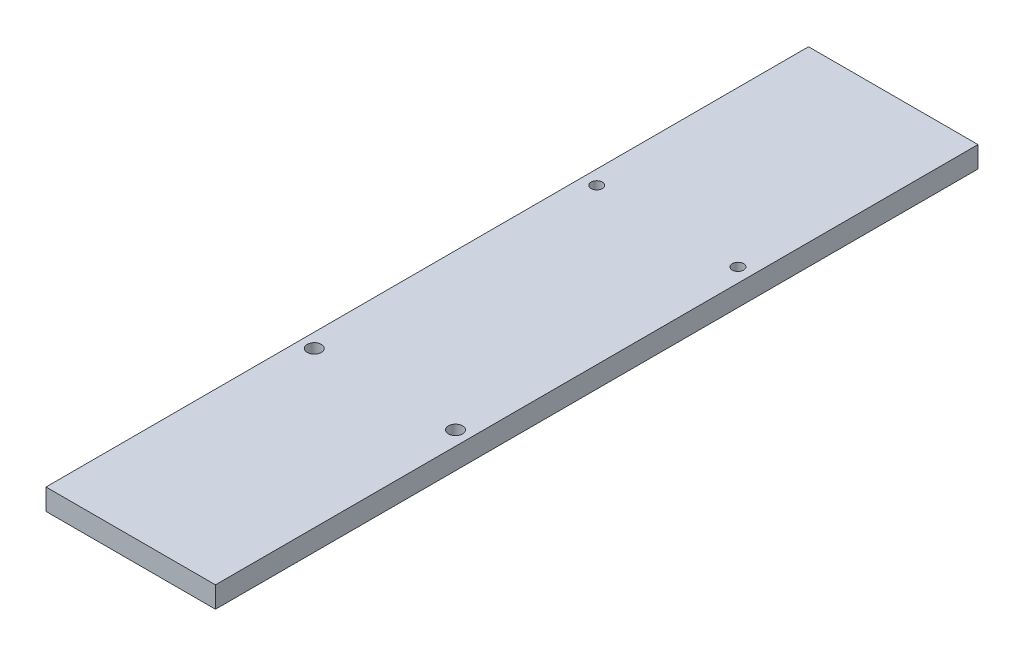
SolidWorks part; units mm, degrees
material "Cedar"
ref_plane "Front Plane" through (0, 0, 0) normal (0, 0, 1) x (1, 0, 0)
ref_plane "Top Plane" through (0, 0, 0) normal (0, 1, 0) x (1, 0, 0)
ref_plane "Right Plane" through (0, 0, 0) normal (1, 0, 0) x (0, 0, -1)
sketch "Sketch1" plane through (0, 0, 0) normal (0, 1, 0) x (1, 0, 0)
  line L1 (0, 0) -> (152.4, 0)
  line L2 (0, 0) -> (0, 685.8)
  line L3 (0, 685.8) -> (152.4, 685.8)
  line L4 (152.4, 0) -> (152.4, 685.8)
  dimension "D1" = 685.8
  dimension "D2" = 152.4
extrude "Boss-Extrude1" add sketch "Sketch1" along normal blind 19.05
sketch "Sketch2" plane through (0, 19.05, 0) normal (0, 1, 0) x (1, 0, 0)
  line L0 (152.4, 685.8) -> (0, 685.8) construction
  line L1 (0, 685.8) -> (0, 0) construction
  line L2 (152.4, 0) -> (152.4, 685.8) construction
  circle A0 centre (12.7, 482.6) radius 5.08
  circle A1 centre (139.7, 482.6) radius 5.08
  circle A2 centre (12.7, 228.6) radius 6.35
  circle A3 centre (139.7, 228.6) radius 6.35
  dimension "D1" = 10.16
  dimension "D5" = 12.7
  dimension "D7" = 12.7
  dimension "D2" = 203.2
  dimension "D3" = 12.7
  dimension "D4" = 12.7
  dimension "D6" = 254
  dimension "D8" = 12.7
extrude "Cut-Extrude1" cut sketch "Sketch2" against normal through all
